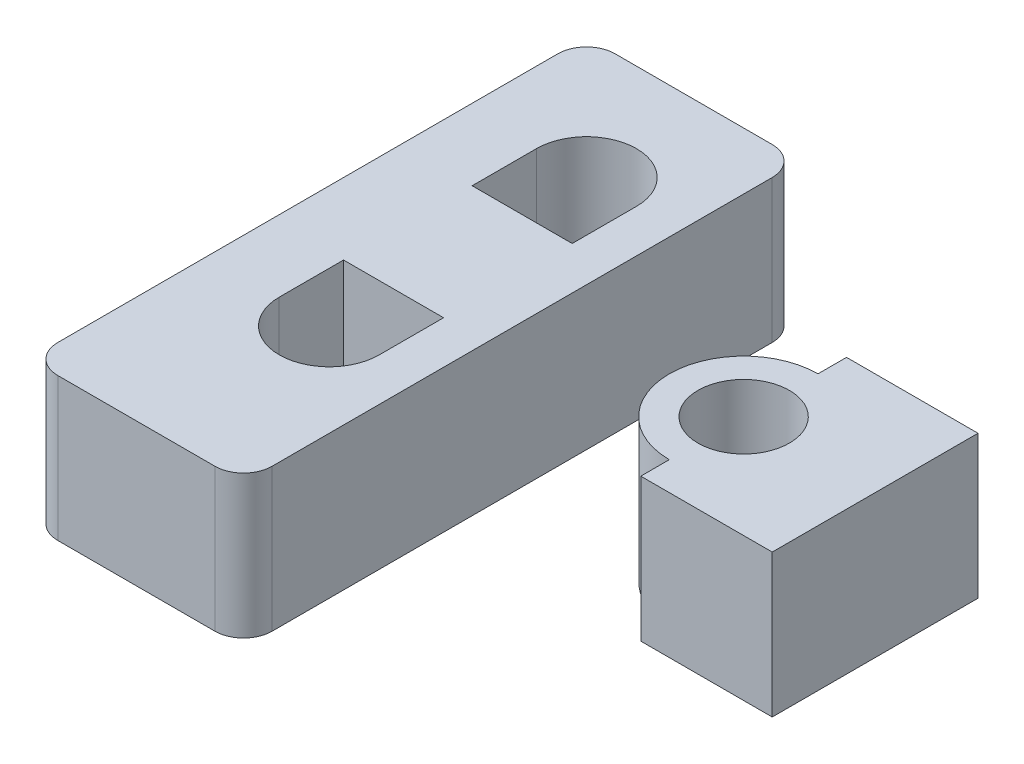
SolidWorks part; units mm, degrees
ref_plane "Front Plane" through (0, 0, 0) normal (0, 0, 1) x (1, 0, 0)
ref_plane "Top Plane" through (0, 0, 0) normal (0, 1, 0) x (1, 0, 0)
ref_plane "Right Plane" through (0, 0, 0) normal (1, 0, 0) x (0, 0, -1)
sketch "Sketch1" plane through (0, 0, 0) normal (0, 1, 0) x (1, 0, 0)
  line L0 (0, -4.5) -> (0, 4.5) construction
  line L1 (-1.75, -4.5) -> (-1.75, 4.5)
  line L2 (1.75, -4.5) -> (1.75, 4.5)
  line L3 (-3.25, -4.5) -> (-3.25, 4.5)
  line L4 (3.25, -4.5) -> (3.25, 4.5)
  arc A0 (-1.75, -4.5) -> (1.75, -4.5) centre (0, -4.5) ccw
  arc A1 (1.75, 4.5) -> (-1.75, 4.5) centre (0, 4.5) ccw
  arc A2 (3.25, 4.5) -> (-3.25, 4.5) centre (0, 4.5) ccw
  arc A3 (-3.25, -4.5) -> (3.25, -4.5) centre (0, -4.5) ccw
  point P2 (0, 0)
  dimension "D2" = 12.5
  dimension "D1" = 3.5
  dimension "D3" = 1.5
extrude "Boss-Extrude1" add sketch "Sketch1" along normal blind 5
sketch "Sketch2" plane through (0, 5, 0) normal (0, 1, 0) x (1, 0, 0)
  line L0 (-1.75, 4.5) -> (-1.75, -4.5) construction
  line L1 (-1.75, 2.25) -> (1.75, 2.25)
  line L2 (-1.75, 2.25) -> (-1.75, -2.25)
  line L3 (-1.75, -2.25) -> (1.75, -2.25)
  line L4 (1.75, 2.25) -> (1.75, -2.25)
  line L5 (1.75, -4.5) -> (1.75, 4.5) construction
  arc A0 (1.75, 4.5) -> (-1.75, 4.5) centre (0, 4.5) ccw construction
  arc A1 (-1.75, -4.5) -> (1.75, -4.5) centre (0, -4.5) ccw construction
  dimension "D1" = 4
  dimension "D2" = 4
extrude "Boss-Extrude2" add sketch "Sketch2" against normal up to surface (5 mm away) up to face at (0, 0, 0)
sketch "Sketch3" plane through (0, 0, 0) normal (0, 1, 0) x (1, 0, 0)
  line L0 (10, -2.6) -> (10, -3.6)
  line L1 (10, -3.6) -> (14.6, -3.6)
  line L2 (14.6, -3.6) -> (14.6, 3.6)
  line L3 (14.6, 3.6) -> (10, 3.6)
  line L4 (10, 3.6) -> (10, 2.6)
  circle A0 centre (10, 0) radius 1.6
  circle A1 centre (10, 0) radius 2.6
  point P7 (0, 0)
  dimension "D1" = 3.2
  dimension "D2" = 1
  dimension "D3" = 5.2
  dimension "D4" = 1
  dimension "D5" = 1
  dimension "D6" = 2
  dimension "D7" = 10
extrude "Boss-Extrude3" add sketch "Sketch3" along normal blind 5 separate body contours A1 A0 | A1 L0 L1 L2 L3 L4 region at (12.8646, 0, 0) region at (7.4735, 0, 0)
sketch "Sketch4" plane through (0, 5, 0) normal (0, 1, 0) x (1, 0, 0)
  line L0 (3.25, 4.5) -> (3.25, 8.75)
  line L1 (3.25, 8.75) -> (-4.25, 8.75)
  line L2 (-4.25, 8.75) -> (-4.25, -10.75)
  line L3 (-4.25, -10.75) -> (3.25, -10.75)
  line L4 (3.25, -10.75) -> (3.25, -4.5)
  line L5 (-3.25, 4.5) -> (-3.25, -4.5) construction
  line L6 (-3.25, 4.5) -> (-3.25, -4.5)
  arc A0 (3.25, 4.5) -> (-3.25, 4.5) centre (0, 4.5) ccw construction
  arc A1 (-3.25, -4.5) -> (3.25, -4.5) centre (0, -4.5) ccw construction
  arc A2 (-3.25, -4.5) -> (3.25, -4.5) centre (0, -4.5) ccw
  arc A3 (3.25, 4.5) -> (-3.25, 4.5) centre (0, 4.5) ccw
  dimension "D2" = 3
  dimension "D1" = 1
  dimension "D3" = 1
extrude "Boss-Extrude4" add sketch "Sketch4" against normal up to surface (5 mm away) up to face at (0, 0, 3.8125)
fillet "Fillet1" radius 1 4 edges at (3.25, 2.5, -8.75) (-4.25, 2.5, -8.75) (-4.25, 2.5, 10.75) (3.25, 2.5, 10.75)
